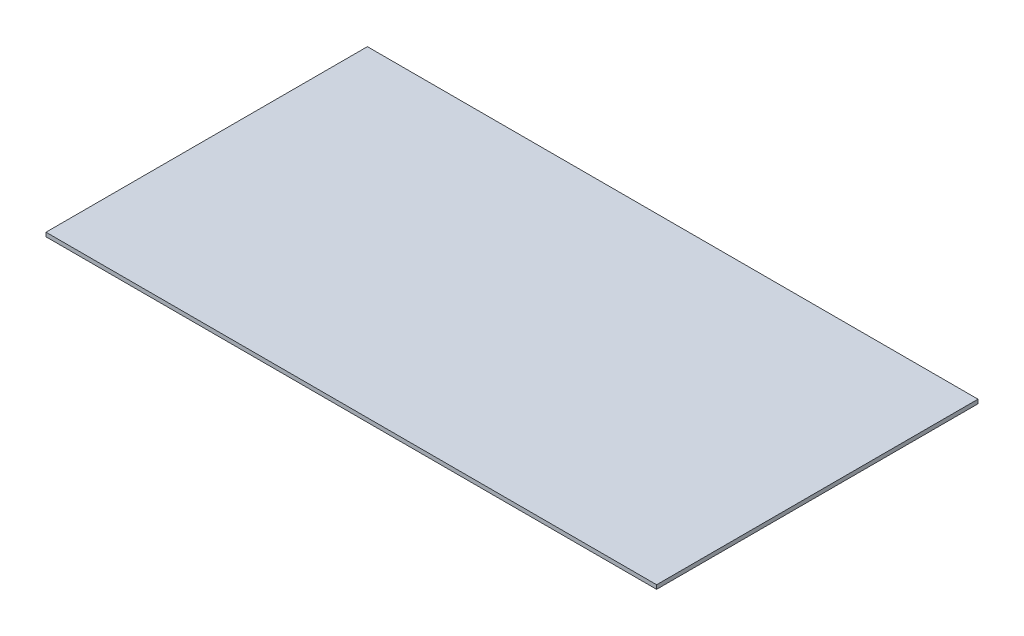
SolidWorks part; units mm, degrees
material "Acrylic (Medium-high impact)"
ref_plane "Front Plane" through (0, 0, 0) normal (0, 0, 1) x (1, 0, 0)
ref_plane "Top Plane" through (0, 0, 0) normal (0, 1, 0) x (1, 0, 0)
ref_plane "Right Plane" through (0, 0, 0) normal (1, 0, 0) x (0, 0, -1)
sketch "Sketch1" plane through (0, 0, 0) normal (0, 1, 0) x (1, 0, 0)
  line L1 (0, 0) -> (482.6, 0)
  line L2 (0, 0) -> (0, 254)
  line L3 (0, 254) -> (482.6, 254)
  line L4 (482.6, 0) -> (482.6, 254)
  dimension "D1" = 254
  dimension "D2" = 482.6
extrude "Boss-Extrude1" add sketch "Sketch1" along normal blind 3.175
